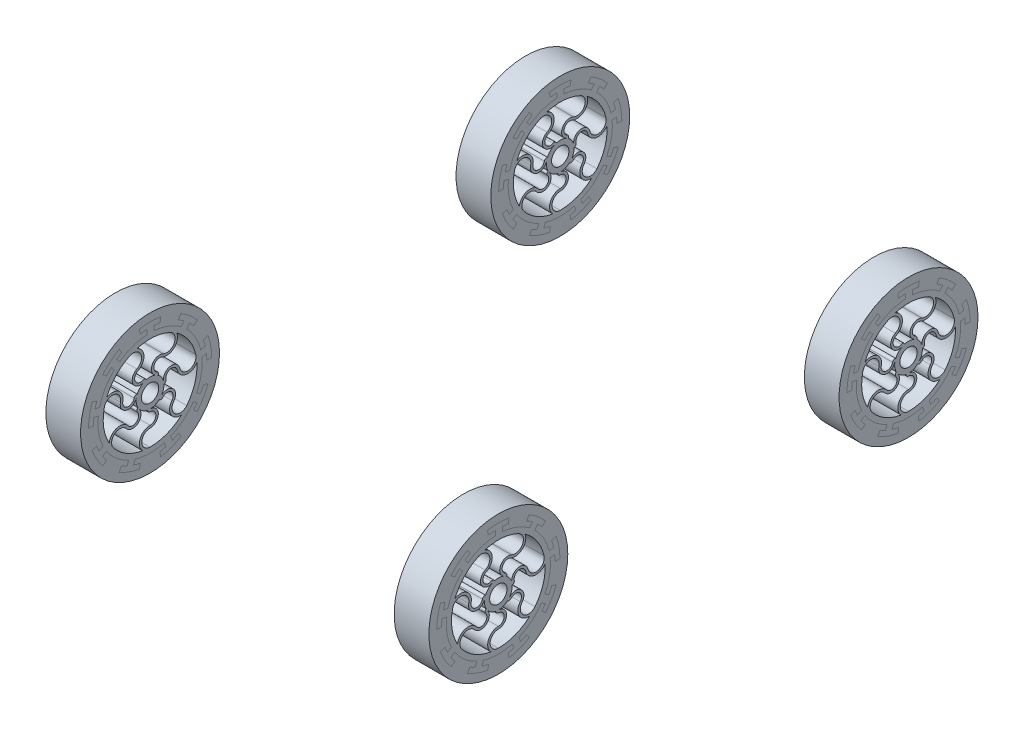
SolidWorks part; units mm, degrees
ref_plane "Front Plane" through (0, 0, 0) normal (0, 0, 1) x (1, 0, 0)
ref_plane "Top Plane" through (0, 0, 0) normal (0, 1, 0) x (1, 0, 0)
ref_plane "Right Plane" through (0, 0, 0) normal (1, 0, 0) x (0, 0, -1)
ref_plane "Plane1" through (57.33, 0, 0) normal (1, 0, 0) x (0, 0, -1)
sketch "Sketch1" plane through (57.33, 0, 0) normal (1, 0, 0) x (0, 0, -1)
  circle A0 centre (0, 0) radius 25.4 construction
  circle A1 centre (0, 0) radius 3.175
  circle A2 centre (0, 0) radius 5.08
  circle A3 centre (0, 0) radius 19.05
  circle A4 centre (0, 0) radius 17.145
  dimension "D1" = 50.8
  dimension "D2" = 38.1
  dimension "D3" = 34.29
  dimension "D4" = 6.35
  dimension "D5" = 10.16
extrude "Boss-Extrude1" add sketch "Sketch1" along normal blind 12.7 contours A3 A4 | A2 A1 region at (57.33, 0, 4.9363) region at (57.33, 0, 18.5112)
sketch "Sketch2" plane through (57.33, 0, 0) normal (1, 0, 0) x (0, 0, -1)
  circle A0 centre (0, 0) radius 5.08
  circle A1 centre (0, 0) radius 17.145
  arc A2 (0, -11.1125) -> (0, -5.08) centre (0, -8.0963) ccw
  arc A3 (0, -11.1125) -> (0, -17.145) centre (0, -14.1288) ccw
  arc A6 (0, -10.2235) -> (-2.7239, -16.9272) centre (0, -14.1288) ccw
  arc A7 (0, -10.2235) -> (0, -5.969) centre (0, -8.0963) ccw
  arc A8 (0, -5.969) -> (-0.8856, -5.0022) centre (0, -5.08) cw
  dimension "D1" = 10.16
  dimension "D2" = 34.29
  dimension "D3" = 0.889
  dimension "D4" = 0
extrude "Boss-Extrude2" add sketch "Sketch2" along normal up to surface (12.7 mm away) contours A8 A7 A6 A1 A3 A2 A0 region at (57.33, -10.6813, 0.5074) up to face at (70.03, 0, -3.175)
pattern_circular "CirPattern1" count 7 over 360 about axis through (70.03, 0, 0) along (1, 0, 0) of "Boss-Extrude2"
sketch "Sketch3" plane through (57.33, 0, 0) normal (1, 0, 0) x (0, 0, -1)
  line L2 (-3.9449, 22.1713) -> (-3.6335, 20.4208)
  line L4 (-1.1102, 20.7118) -> (-1.1102, 19.0176)
  line L6 (3.9449, 22.1713) -> (3.6335, 20.4208)
  line L7 (1.4298, 20.6921) -> (1.4298, 18.9963)
  circle A0 centre (0, 0) radius 19.05 construction
  circle A1 centre (0, 0) radius 19.05
  arc A2 (-3.9449, 22.1713) -> (3.9449, 22.1713) centre (0, 0) cw
  arc A3 (-3.6335, 20.4208) -> (-1.1102, 20.7118) centre (0, 0) cw
  arc A4 (1.4298, 20.6921) -> (3.6335, 20.4208) centre (0, 0) cw
  point P16 (0, 0)
  point P17 (-3.9421, 22.3897)
  point P18 (1.294, 20.9135)
  point P19 (-1.1102, 21.863)
  point P20 (0, 0)
  dimension "D5" = 2.5401
  dimension "D1" = 2.54
  dimension "D2" = 1.778
  dimension "D3" = 2.54
  dimension "D4" = 3.175
extrude "Boss-Extrude3" add sketch "Sketch3" along a picked direction on the side of the normal blind 12.7 contours A1 L7 L6 A2 L2 A3 L4 region at (57.33, 21.1336, -0.0386)
pattern_circular "CirPattern2" count 9 over 360 about axis through (70.03, 0, 0) along (1, 0, 0) of "Boss-Extrude3"
sketch "Sketch5" plane through (57.33, 0, 0) normal (1, 0, 0) x (0, 0, -1)
  line L36 (-1.1102, 20.7118) -> (-1.1102, 19.0176)
  line L37 (-3.9449, 22.1713) -> (-3.6335, 20.4208)
  line L38 (3.6335, 20.4208) -> (3.9449, 22.1713)
  line L39 (1.4298, 18.9963) -> (1.4298, 20.6921)
  line L40 (12.4628, 16.5797) -> (11.3738, 15.282)
  line L41 (11.2294, 19.5199) -> (10.3428, 17.9787)
  line L42 (15.9096, 13.3077) -> (17.2734, 14.4484)
  line L43 (13.3059, 13.6329) -> (14.396, 14.932)
  line L44 (20.2043, 4.6899) -> (18.5359, 4.3957)
  line L45 (21.1494, 7.735) -> (19.4796, 7.1243)
  line L46 (20.7415, -0.0322) -> (22.5195, -0.035)
  line L47 (18.956, 1.8906) -> (20.6261, 2.1851)
  line L48 (18.492, -9.3944) -> (17.0248, -8.5474)
  line L49 (21.1733, -7.6692) -> (19.5016, -7.0637)
  line L50 (15.8682, -13.357) -> (17.2284, -14.502)
  line L51 (15.7363, -10.7364) -> (17.205, -11.5843)
  line L52 (8.1271, -19.083) -> (7.5476, -17.491)
  line L53 (11.29, -19.4849) -> (10.3986, -17.9465)
  line L54 (3.57, -20.432) -> (3.876, -22.1834)
  line L55 (5.1535, -18.3397) -> (5.7335, -19.9333)
  line L56 (-6.0406, -19.8424) -> (-5.4612, -18.2504)
  line L57 (-3.876, -22.1834) -> (-3.57, -20.432)
  line L58 (-10.3986, -17.9465) -> (-11.29, -19.4849)
  line L59 (-7.8407, -17.3616) -> (-8.4207, -18.9552)
  line L60 (-17.3818, -11.3173) -> (-15.9147, -10.4703)
  line L61 (-17.2284, -14.502) -> (-15.8682, -13.357)
  line L62 (-19.5016, -7.0637) -> (-21.1733, -7.6692)
  line L63 (-17.1662, -8.2599) -> (-18.6348, -9.1078)
  line L64 (-20.5899, 2.5032) -> (-18.9215, 2.2091)
  line L65 (-22.5195, -0.035) -> (-20.7415, -0.0322)
  line L66 (-19.4796, 7.1243) -> (-21.1494, 7.735)
  line L67 (-18.4594, 4.7068) -> (-20.1295, 5.0013)
  line L68 (-14.1637, 15.1525) -> (-13.0747, 13.8547)
  line L69 (-17.2734, 14.4484) -> (-15.9096, 13.3077)
  line L70 (-10.3428, 17.9787) -> (-11.2294, 19.5199)
  line L71 (-11.1153, 15.4711) -> (-12.2054, 16.7702)
  line L72 (-1.1102, 20.7118) -> (-1.1102, 19.0176)
  line L73 (-3.9449, 22.1713) -> (-3.6335, 20.4208)
  line L74 (3.6335, 20.4208) -> (3.9449, 22.1713)
  line L75 (1.4298, 18.9963) -> (1.4298, 20.6921)
  line L76 (12.4628, 16.5797) -> (11.3738, 15.282)
  line L77 (11.2294, 19.5199) -> (10.3428, 17.9787)
  line L78 (15.9096, 13.3077) -> (17.2734, 14.4484)
  line L79 (13.3059, 13.6329) -> (14.396, 14.932)
  line L80 (20.2043, 4.6899) -> (18.5359, 4.3957)
  line L81 (21.1494, 7.735) -> (19.4796, 7.1243)
  line L82 (20.7415, -0.0322) -> (22.5195, -0.035)
  line L83 (18.956, 1.8906) -> (20.6261, 2.1851)
  line L84 (18.492, -9.3944) -> (17.0248, -8.5474)
  line L85 (21.1733, -7.6692) -> (19.5016, -7.0637)
  line L86 (15.8682, -13.357) -> (17.2284, -14.502)
  line L87 (15.7363, -10.7364) -> (17.205, -11.5843)
  line L88 (8.1271, -19.083) -> (7.5476, -17.491)
  line L89 (11.29, -19.4849) -> (10.3986, -17.9465)
  line L90 (3.57, -20.432) -> (3.876, -22.1834)
  line L91 (5.1535, -18.3397) -> (5.7335, -19.9333)
  line L92 (-6.0406, -19.8424) -> (-5.4612, -18.2504)
  line L93 (-3.876, -22.1834) -> (-3.57, -20.432)
  line L94 (-10.3986, -17.9465) -> (-11.29, -19.4849)
  line L95 (-7.8407, -17.3616) -> (-8.4207, -18.9552)
  line L96 (-17.3818, -11.3173) -> (-15.9147, -10.4703)
  line L97 (-17.2284, -14.502) -> (-15.8682, -13.357)
  line L98 (-19.5016, -7.0637) -> (-21.1733, -7.6692)
  line L99 (-17.1662, -8.2599) -> (-18.6348, -9.1078)
  line L100 (-20.5899, 2.5032) -> (-18.9215, 2.2091)
  line L101 (-22.5195, -0.035) -> (-20.7415, -0.0322)
  line L102 (-19.4796, 7.1243) -> (-21.1494, 7.735)
  line L103 (-18.4594, 4.7068) -> (-20.1295, 5.0013)
  line L104 (-14.1637, 15.1525) -> (-13.0747, 13.8547)
  line L105 (-17.2734, 14.4484) -> (-15.9096, 13.3077)
  line L106 (-10.3428, 17.9787) -> (-11.2294, 19.5199)
  line L107 (-11.1153, 15.4711) -> (-12.2054, 16.7702)
  circle A0 centre (0, 0) radius 25.4
  arc A37 (-1.1102, 19.0176) -> (-11.1153, 15.4711) centre (0, 0) ccw
  arc A38 (-1.1102, 20.7118) -> (-3.6335, 20.4208) centre (0, 0) ccw
  arc A39 (3.9449, 22.1713) -> (-3.9449, 22.1713) centre (0, 0) ccw
  arc A40 (3.6335, 20.4208) -> (1.4298, 20.6921) centre (0, 0) ccw
  arc A41 (11.3738, 15.282) -> (1.4298, 18.9963) centre (0, 0) ccw
  arc A42 (12.4628, 16.5797) -> (10.3428, 17.9787) centre (0, 0) ccw
  arc A43 (17.2734, 14.4484) -> (11.2294, 19.5199) centre (0, 0) ccw
  arc A44 (15.9096, 13.3077) -> (14.396, 14.932) centre (0, 0) ccw
  arc A45 (18.5359, 4.3957) -> (13.3059, 13.6329) centre (0, 0) ccw
  arc A46 (20.2043, 4.6899) -> (19.4796, 7.1243) centre (0, 0) ccw
  arc A47 (22.5195, -0.035) -> (21.1494, 7.735) centre (0, 0) ccw
  arc A48 (20.7415, -0.0322) -> (20.6261, 2.1851) centre (0, 0) ccw
  arc A49 (17.0248, -8.5474) -> (18.956, 1.8906) centre (0, 0) ccw
  arc A50 (18.492, -9.3944) -> (19.5016, -7.0637) centre (0, 0) ccw
  arc A51 (17.2284, -14.502) -> (21.1733, -7.6692) centre (0, 0) ccw
  arc A52 (15.8682, -13.357) -> (17.205, -11.5843) centre (0, 0) ccw
  arc A53 (7.5476, -17.491) -> (15.7363, -10.7364) centre (0, 0) ccw
  arc A54 (8.1271, -19.083) -> (10.3986, -17.9465) centre (0, 0) ccw
  arc A55 (3.876, -22.1834) -> (11.29, -19.4849) centre (0, 0) ccw
  arc A56 (3.57, -20.432) -> (5.7335, -19.9333) centre (0, 0) ccw
  arc A57 (-5.4612, -18.2504) -> (5.1535, -18.3397) centre (0, 0) ccw
  arc A58 (-6.0406, -19.8424) -> (-3.57, -20.432) centre (0, 0) ccw
  arc A59 (-11.29, -19.4849) -> (-3.876, -22.1834) centre (0, 0) ccw
  arc A60 (-10.3986, -17.9465) -> (-8.4207, -18.9552) centre (0, 0) ccw
  arc A61 (-15.9147, -10.4703) -> (-7.8407, -17.3616) centre (0, 0) ccw
  arc A62 (-17.3818, -11.3173) -> (-15.8682, -13.357) centre (0, 0) ccw
  arc A63 (-21.1733, -7.6692) -> (-17.2284, -14.502) centre (0, 0) ccw
  arc A64 (-19.5016, -7.0637) -> (-18.6348, -9.1078) centre (0, 0) ccw
  arc A65 (-18.9215, 2.2091) -> (-17.1662, -8.2599) centre (0, 0) ccw
  arc A66 (-20.5899, 2.5032) -> (-20.7415, -0.0322) centre (0, 0) ccw
  arc A67 (-21.1494, 7.735) -> (-22.5195, -0.035) centre (0, 0) ccw
  arc A68 (-19.4796, 7.1243) -> (-20.1295, 5.0013) centre (0, 0) ccw
  arc A69 (-13.0747, 13.8547) -> (-18.4594, 4.7068) centre (0, 0) ccw
  arc A70 (-14.1637, 15.1525) -> (-15.9096, 13.3077) centre (0, 0) ccw
  arc A71 (-11.2294, 19.5199) -> (-17.2734, 14.4484) centre (0, 0) ccw
  arc A72 (-10.3428, 17.9787) -> (-12.2054, 16.7702) centre (0, 0) ccw
  arc A73 (-1.1102, 19.0176) -> (-11.1153, 15.4711) centre (0, 0) ccw
  arc A74 (-1.1102, 20.7118) -> (-3.6335, 20.4208) centre (0, 0) ccw
  arc A75 (3.9449, 22.1713) -> (-3.9449, 22.1713) centre (0, 0) ccw
  arc A76 (3.6335, 20.4208) -> (1.4298, 20.6921) centre (0, 0) ccw
  arc A77 (11.3738, 15.282) -> (1.4298, 18.9963) centre (0, 0) ccw
  arc A78 (12.4628, 16.5797) -> (10.3428, 17.9787) centre (0, 0) ccw
  arc A79 (17.2734, 14.4484) -> (11.2294, 19.5199) centre (0, 0) ccw
  arc A80 (15.9096, 13.3077) -> (14.396, 14.932) centre (0, 0) ccw
  arc A81 (18.5359, 4.3957) -> (13.3059, 13.6329) centre (0, 0) ccw
  arc A82 (20.2043, 4.6899) -> (19.4796, 7.1243) centre (0, 0) ccw
  arc A83 (22.5195, -0.035) -> (21.1494, 7.735) centre (0, 0) ccw
  arc A84 (20.7415, -0.0322) -> (20.6261, 2.1851) centre (0, 0) ccw
  arc A85 (17.0248, -8.5474) -> (18.956, 1.8906) centre (0, 0) ccw
  arc A86 (18.492, -9.3944) -> (19.5016, -7.0637) centre (0, 0) ccw
  arc A87 (17.2284, -14.502) -> (21.1733, -7.6692) centre (0, 0) ccw
  arc A88 (15.8682, -13.357) -> (17.205, -11.5843) centre (0, 0) ccw
  arc A89 (7.5476, -17.491) -> (15.7363, -10.7364) centre (0, 0) ccw
  arc A90 (8.1271, -19.083) -> (10.3986, -17.9465) centre (0, 0) ccw
  arc A91 (3.876, -22.1834) -> (11.29, -19.4849) centre (0, 0) ccw
  arc A92 (3.57, -20.432) -> (5.7335, -19.9333) centre (0, 0) ccw
  arc A93 (-5.4612, -18.2504) -> (5.1535, -18.3397) centre (0, 0) ccw
  arc A94 (-6.0406, -19.8424) -> (-3.57, -20.432) centre (0, 0) ccw
  arc A95 (-11.29, -19.4849) -> (-3.876, -22.1834) centre (0, 0) ccw
  arc A96 (-10.3986, -17.9465) -> (-8.4207, -18.9552) centre (0, 0) ccw
  arc A97 (-15.9147, -10.4703) -> (-7.8407, -17.3616) centre (0, 0) ccw
  arc A98 (-17.3818, -11.3173) -> (-15.8682, -13.357) centre (0, 0) ccw
  arc A99 (-21.1733, -7.6692) -> (-17.2284, -14.502) centre (0, 0) ccw
  arc A100 (-19.5016, -7.0637) -> (-18.6348, -9.1078) centre (0, 0) ccw
  arc A101 (-18.9215, 2.2091) -> (-17.1662, -8.2599) centre (0, 0) ccw
  arc A102 (-20.5899, 2.5032) -> (-20.7415, -0.0322) centre (0, 0) ccw
  arc A103 (-21.1494, 7.735) -> (-22.5195, -0.035) centre (0, 0) ccw
  arc A104 (-19.4796, 7.1243) -> (-20.1295, 5.0013) centre (0, 0) ccw
  arc A105 (-13.0747, 13.8547) -> (-18.4594, 4.7068) centre (0, 0) ccw
  arc A106 (-14.1637, 15.1525) -> (-15.9096, 13.3077) centre (0, 0) ccw
  arc A107 (-11.2294, 19.5199) -> (-17.2734, 14.4484) centre (0, 0) ccw
  arc A108 (-10.3428, 17.9787) -> (-12.2054, 16.7702) centre (0, 0) ccw
  dimension "D1" = 50.8
  dimension "D2" = 0
extrude "Boss-Extrude4" add sketch "Sketch5" along normal up to surface (12.7 mm away) separate body up to face at (70.03, -8.4949, 4.395)
sketch "Sketch4" plane through (0, 0, 0) normal (1, 0, 0) x (0, 0, -1)
  line L0 (0, 0) -> (-150, 0) construction
  point P2 (-12.4551, 0)
  point P4 (0, 0)
pattern_linear "LPattern1" count 2 spacing 150 along (0, 0, 1) of bodies 111 107
mirror "Mirror1" about plane through (0, 0, 0) normal (1, 0, 0) of bodies 107 108 112 111
